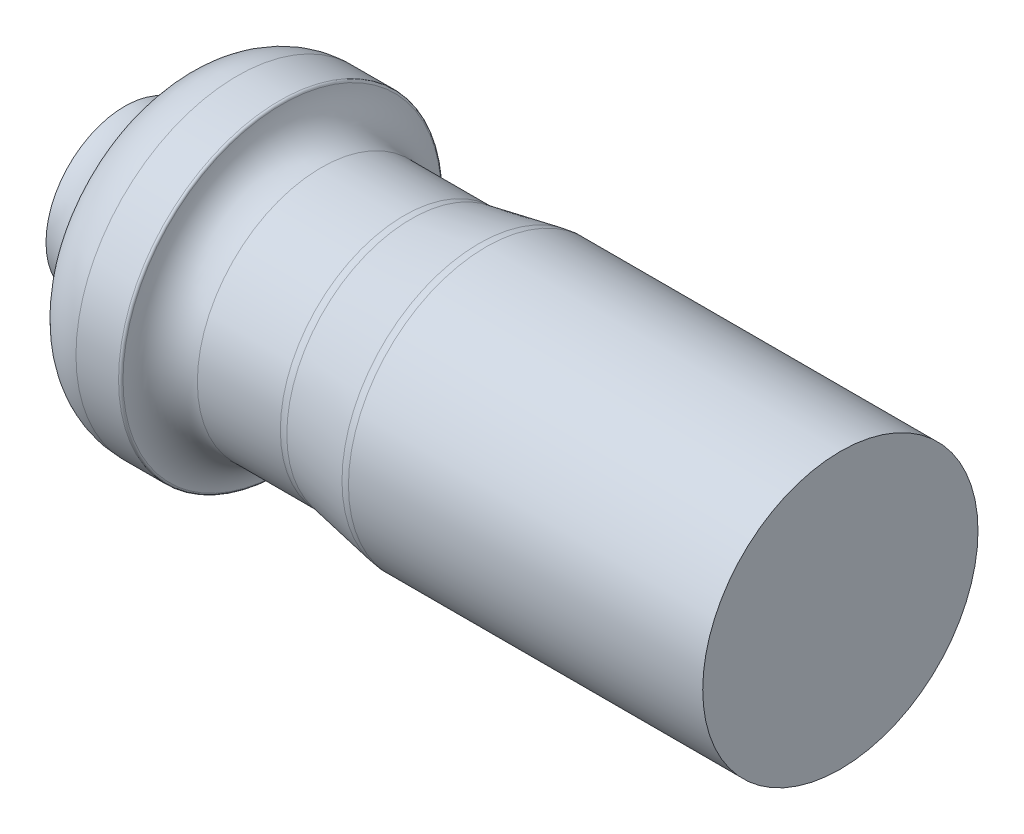
SolidWorks part; units mm, degrees
ref_plane "Front Plane" through (0, 0, 0) normal (0, 0, 1) x (1, 0, 0)
ref_plane "Top Plane" through (0, 0, 0) normal (0, 1, 0) x (1, 0, 0)
ref_plane "Right Plane" through (0, 0, 0) normal (1, 0, 0) x (0, 0, -1)
sketch "Sketch3" plane through (0, 0, 0) normal (0, 0, 1) x (1, 0, 0)
  line L0 (0, 0) -> (0, -50000) construction
  line L1 (0, 0) -> (50000, 0) construction
  line L2 (45.5, 0) -> (45.5, 17.5)
  line L3 (45.5, 17.5) -> (0, 17.5)
  line L4 (0, 17.5) -> (-9.5, 15.75)
  line L5 (-9.5, 15.75) -> (-25.5, 15.75)
  line L6 (-25.5, 15.75) -> (-25.5, 20.5)
  line L7 (-45.5, 0) -> (-45.5, 53.8042) construction
  line L8 (-25.5, 20.5) -> (-31.1909, 20.5)
  line L9 (-45.5, 10) -> (-36.3733, 10) construction
  line L10 (-45.5, 10) -> (-45.5, 0)
  line L11 (-45.5, 0) -> (45.5, 0)
  arc A0 (-45.5, 10) -> (-38.8224, 14.9) centre (-45.5, 17) ccw
  arc A1 (-38.8224, 14.9) -> (-31.1909, 20.5) centre (-31.1909, 12.5) cw
  dimension "D8" = 20
  dimension "D9" = 7
  dimension "D10" = 8
  dimension "D1" = 17.5
  dimension "D2" = 45.5
  dimension "D3" = 9.5
  dimension "D4" = 31.5
  dimension "D5" = 41
  dimension "D6" = 71
  dimension "D7" = 20
revolve "Revolve1" add sketch "Sketch3" angle 360 about L1
fillet "Fillet1" radius 5 1 edges at (-25.5, 0, 15.75)
fillet "Fillet2" radius 0.3 1 edges at (-25.5, 0, 20.5)
fillet "Fillet3" radius 5 2 edges at (0, 0, 17.5) (-9.5, 0, 15.75)
